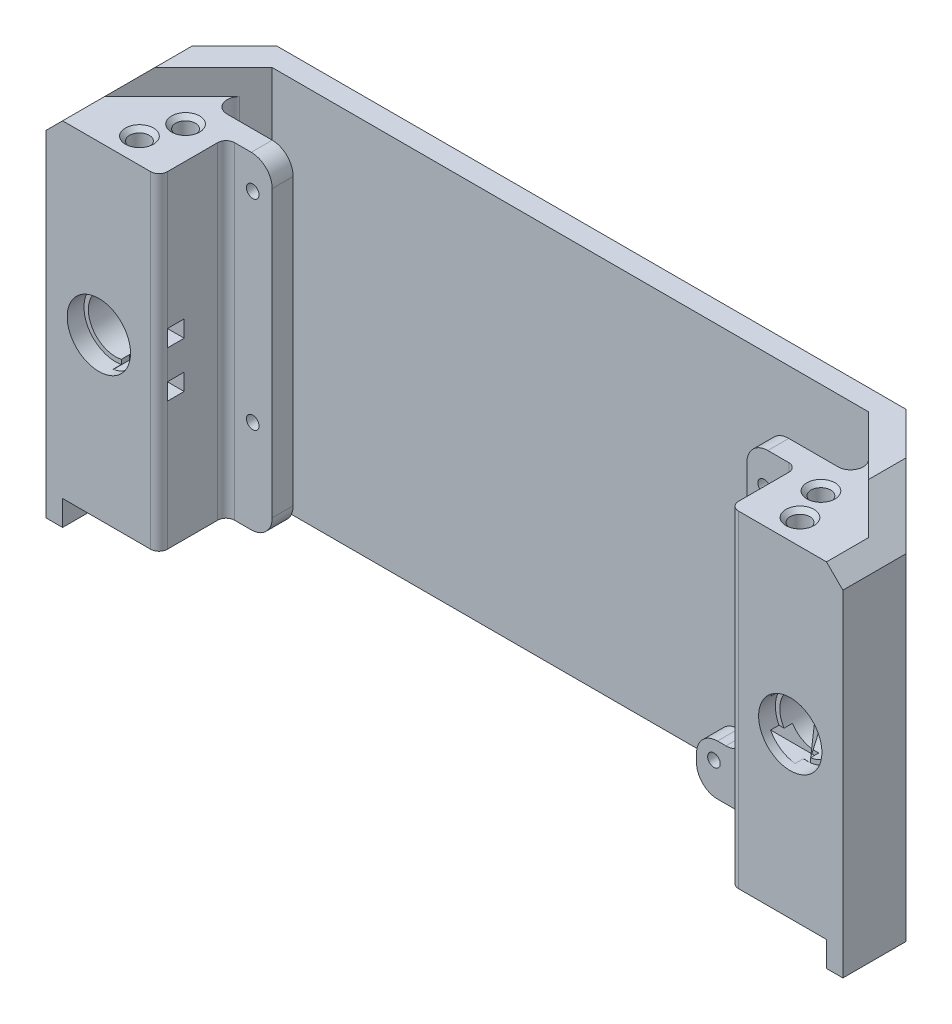
SolidWorks part; units mm, degrees
ref_plane "Front Plane" through (0, 0, 0) normal (0, 0, 1) x (1, 0, 0)
ref_plane "Top Plane" through (0, 0, 0) normal (0, 1, 0) x (1, 0, 0)
ref_plane "Right Plane" through (0, 0, 0) normal (1, 0, 0) x (0, 0, -1)
sketch "Sketch1" plane through (0, 0, 0) normal (0, 0, 1) x (1, 0, 0)
  line L1 (-95, 45) -> (95, 45)
  line L2 (-95, 45) -> (-95, -45)
  line L3 (-95, -45) -> (95, -45)
  line L4 (95, 45) -> (95, -45)
  line L5 (-95, 45) -> (95, -45) construction
  line L6 (-95, -45) -> (95, 45) construction
  point P0 (0, 0)
  point P6 (0, 0)
  dimension "D2" = 190
  dimension "D4" = 90
extrude "Boss-Extrude1" add sketch "Sketch1" along normal blind 5
sketch "Sketch2" plane through (0, 0, 5) normal (0, 0, 1) x (1, 0, 0)
  line L0 (-95, -45) -> (95, -45) construction
  line L1 (-95, 45) -> (-91.1, 45)
  line L2 (-95, 45) -> (-95, -45)
  line L3 (-95, -45) -> (-91.1, -45)
  line L4 (-91.1, 45) -> (-91.1, -45)
  line L5 (0, 0) -> (0, 45) construction
  line L6 (95, 45) -> (-95, 45) construction
  line L7 (95, -45) -> (91.1, -45)
  line L8 (91.1, 45) -> (91.1, -45)
  line L9 (95, 45) -> (91.1, 45)
  line L10 (95, 45) -> (95, -45)
  dimension "D1" = 3.9
extrude "Boss-Extrude2" add sketch "Sketch2" along normal blind 30
sketch "Sketch3" plane through (0, 45, 0) normal (0, 1, 0) x (1, 0, 0)
  line L0 (-91.1, -35) -> (-91.1, -5) construction
  line L1 (-91.1, -14) -> (-57.1, -14)
  line L2 (-91.1, -14) -> (-91.1, -19)
  line L3 (-91.1, -19) -> (-57.1, -19)
  line L4 (-57.1, -14) -> (-57.1, -19)
  line L5 (91.1, -35) -> (91.1, -5) construction
  line L6 (91.1, -14) -> (44.1, -14)
  line L7 (91.1, -14) -> (91.1, -19)
  line L8 (91.1, -19) -> (44.1, -19)
  line L9 (44.1, -14) -> (44.1, -19)
  line L10 (91.1, -5) -> (-91.1, -5) construction
  dimension "D1" = 9
  dimension "D2" = 9
  dimension "D3" = 5
  dimension "D4" = 5
  dimension "D5" = 34
  dimension "D6" = 47
extrude "Boss-Extrude3" add sketch "Sketch3" against normal up to surface (90 mm away) up to face at (0, -45, 18.75)
sketch "Sketch4" plane through (0, 0, 19) normal (0, 0, 1) x (1, 0, 0)
  line L0 (91.1, -45) -> (91.1, 45) construction
  line L1 (-91.1, 45) -> (91.1, 45)
  line L2 (-91.1, 45) -> (-91.1, 39)
  line L3 (-91.1, 39) -> (91.1, 39)
  line L4 (91.1, 45) -> (91.1, 39)
  line L5 (0, 0) -> (-91.1, 0) construction
  line L6 (-91.1, -45) -> (-91.1, 45) construction
  line L7 (-91.1, -39) -> (91.1, -39)
  line L8 (91.1, -45) -> (91.1, -39)
  line L9 (-91.1, -45) -> (91.1, -45)
  line L10 (-91.1, -45) -> (-91.1, -39)
  dimension "D1" = 6
extrude "Cut-Extrude1" cut sketch "Sketch4" against normal blind 5
sketch "Sketch5" plane through (0, 0, 19) normal (0, 0, 1) x (1, 0, 0)
  line L0 (0, 0) -> (-61.75, 0) construction
  line L1 (-70.2, 37.38) -> (70.2, 37.38) construction
  line L2 (-70.2, 37.38) -> (-70.2, -37.38) construction
  line L3 (-70.2, -37.38) -> (70.2, -37.38) construction
  line L4 (70.2, 37.38) -> (70.2, -37.38) construction
  line L5 (-70.2, 37.38) -> (70.2, -37.38) construction
  line L6 (-70.2, -37.38) -> (70.2, 37.38) construction
  line L7 (-61.75, 0) -> (-61.75, 31.13) construction
  line L8 (-61.75, 0) -> (-61.75, -16.61) construction
  line L9 (48.25, 0) -> (60.23, 0) construction
  line L10 (60.23, 0) -> (60.23, 31.13) construction
  line L11 (0, 0) -> (48.25, 0) construction
  line L12 (48.25, 0) -> (48.25, -31.38) construction
  circle A0 centre (-61.75, 31.13) radius 1.5
  circle A1 centre (-61.75, -16.61) radius 1.5
  circle A2 centre (60.23, 31.13) radius 1.5
  circle A3 centre (48.25, -31.38) radius 1.5
  point P0 (0, 0)
  dimension "D10" = 3
  dimension "D11" = 3
  dimension "D12" = 3
  dimension "D13" = 3
  dimension "D1" = 140.4
  dimension "D2" = 74.76
  dimension "D3" = 61.75
  dimension "D4" = 31.13
  dimension "D5" = 16.61
  dimension "D6" = 60.23
  dimension "D7" = 31.13
  dimension "D8" = 48.25
  dimension "D9" = 31.38
extrude "Cut-Extrude2" cut sketch "Sketch5" against normal up to surface (5 mm away) up to face at (67.6, 0, 14)
sketch "Sketch6" plane through (0, 0, 19) normal (0, 0, 1) x (1, 0, 0)
  line L1 (44.1, 39) -> (56.1, 39)
  line L2 (44.1, 39) -> (44.1, -27)
  line L3 (44.1, -27) -> (56.1, -27)
  line L4 (56.1, 39) -> (56.1, -27)
  dimension "D1" = 12
  dimension "D2" = 66
extrude "Cut-Extrude3" cut sketch "Sketch6" against normal up to surface (5 mm away) up to face at (46.75, -31.38, 14)
chamfer "Chamfer6" distance 20 angle 45 4 edges at (91.1, 0, 5) (95, 0, 0) (-95, 0, 0) (-91.1, 0, 5)
sketch "Sketch7" plane through (0, 39, 0) normal (0, 1, 0) x (1, 0, 0)
  line L0 (-85.1, -19) -> (-91.1, -25)
  line L1 (-91.1, -25) -> (-91.1, -35)
  line L2 (-91.1, -35) -> (-68.1, -35)
  line L3 (-68.1, -35) -> (-68.1, -19)
  line L4 (-85.1, -19) -> (-57.1, -19) construction
  line L5 (-68.1, -19) -> (-85.1, -19)
  line L6 (0, 0) -> (0, -5) construction
  line L7 (71.1, -5) -> (-71.1, -5) construction
  line L8 (68.1, -35) -> (68.1, -19)
  line L9 (91.1, -35) -> (68.1, -35)
  line L10 (91.1, -25) -> (91.1, -35)
  line L11 (85.1, -19) -> (91.1, -25)
  line L12 (68.1, -19) -> (85.1, -19)
  dimension "D1" = 23
extrude "Boss-Extrude4" add sketch "Sketch7" against normal up to surface (78 mm away) up to face at (-69.85, -39, 16.5)
fillet "Fillet4" radius 5 6 edges at (-57.1, -39, 16.5) (-57.1, 39, 16.5) (56.1, 39, 16.5) (44.1, -39, 16.5) (44.1, -27, 16.5) (56.1, -27, 16.5)
fillet "Fillet5" radius 2 4 edges at (-68.1, 0, 35) (68.1, 0, 35) (68.1, 0, 19) (-68.1, 0, 19)
fillet "Fillet6" radius 3 2 edges at (-80.1, 0, 14) (80.1, 0, 14)
sketch "Sketch9" plane through (0, 0, 35) normal (0, 0, 1) x (1, 0, 0)
  line L6 (0, 0) -> (0, -45) construction
  line L7 (-71.1, -45) -> (71.1, -45) construction
  line L8 (-95, 45) -> (-95, -45) construction
  line L9 (-95, 39) -> (-82.45, 39) construction
  line L10 (-95, 39) -> (-95, -0.9074) construction
  line L11 (-95, -0.9074) -> (-82.45, -0.9074) construction
  line L12 (-82.45, 39) -> (-82.45, -0.9074) construction
  line L13 (-91.1, 39) -> (-70.1, 39) construction
  circle A0 centre (-82.45, -0.9074) radius 6.5
  circle A1 centre (82.45, -0.9074) radius 6.5
  dimension "D3" = 13
  dimension "D1" = 39.9074
  dimension "D2" = 12.55
extrude "Cut-Extrude4" cut sketch "Sketch9" against normal blind 10
sketch "Sketch10" plane through (0, 0, 35) normal (0, 0, 1) x (1, 0, 0)
  circle A0 centre (-82.45, -0.9074) radius 7.55
  circle A1 centre (82.45, -0.9074) radius 7.55
  dimension "D1" = 15.1
  dimension "D2" = 15.1
extrude "Cut-Extrude5" cut sketch "Sketch10" against normal blind 4
sketch "Sketch12" plane through (-68.1, 0, 0) normal (1, 0, 0) x (0, 0, -1)
  line L0 (-33, -4.4074) -> (-29, -4.4074)
  line L1 (-33, 39) -> (-23, 39) construction
  line L2 (-33, 39) -> (-33, -0.9074) construction
  line L3 (-33, -0.9074) -> (-23, -0.9074) construction
  line L4 (-23, 39) -> (-23, -0.9074) construction
  line L5 (-33, 6.5926) -> (-23, 6.5926) construction
  line L6 (-33, 6.5926) -> (-33, -8.4074) construction
  line L7 (-33, -8.4074) -> (-23, -8.4074) construction
  line L8 (-23, 6.5926) -> (-23, -8.4074) construction
  line L9 (-33, 6.5926) -> (-23, -8.4074) construction
  line L10 (-33, -8.4074) -> (-23, 6.5926) construction
  line L11 (-33, 6.5926) -> (-29, 6.5926)
  line L12 (-33, 6.5926) -> (-33, 2.5926)
  line L13 (-33, 2.5926) -> (-29, 2.5926)
  line L14 (-29, 6.5926) -> (-29, 2.5926)
  line L15 (-29, -8.4074) -> (-29, -4.4074)
  line L16 (-33, -8.4074) -> (-29, -8.4074)
  line L17 (-33, -8.4074) -> (-33, -4.4074)
  point P5 (-28, -0.9074)
  dimension "D1" = 39.9074
  dimension "D2" = 10
  dimension "D3" = 15
  dimension "D4" = 10
  dimension "D5" = 4
  dimension "D6" = 4
extrude "Cut-Extrude6" cut sketch "Sketch12" against normal blind 13 and the other way blind 151.4
sketch "Sketch15" plane through (0, 39, 0) normal (0, 1, 0) x (1, 0, 0)
  line L0 (68.1, -21) -> (68.1, -33) construction
  line L5 (72.8574, -14) -> (61.1, -14) construction
  line L6 (91.1, -35) -> (68.1, -35) construction
  line L7 (91.1, -35) -> (91.1, -14) construction
  line L8 (91.1, -14) -> (68.1, -14) construction
  line L9 (68.1, -35) -> (68.1, -14) construction
  line L10 (68.1, -14) -> (75.7667, -21) construction
  line L11 (75.7667, -21) -> (83.4333, -28) construction
  line L12 (83.4333, -28) -> (91.1, -35) construction
  line L13 (0, 0) -> (0, -5) construction
  line L14 (71.1, -5) -> (-71.1, -5) construction
  line L15 (75.7667, -21) -> (75.7667, -29) construction
  line L16 (75.7667, -29) -> (78.7667, -29) construction
  circle A0 centre (75.7667, -21) radius 2.35
  circle A1 centre (83.4333, -28) radius 2.35 construction
  circle A2 centre (-75.7667, -21) radius 2.35
  circle A3 centre (-83.4333, -28) radius 2.35 construction
  circle A6 centre (78.7667, -29) radius 2.35
  circle A7 centre (-78.7667, -29) radius 2.35
  dimension "D1" = 4.7
  dimension "D2" = 4.7
  dimension "D5" = 4.7
  dimension "D3" = 23
  dimension "D4" = 21
  dimension "D6" = 8
  dimension "D7" = 3
extrude "Cut-Extrude7" cut sketch "Sketch15" against normal blind 8
chamfer "Chamfer7" distance 1 angle 45 4 edges at (-75.7667, 39, 18.65) (75.7667, 39, 23.35) (-78.7667, 39, 26.65) (78.7667, 39, 31.35)
sketch "Sketch17" plane through (0, -39, 0) normal (0, -1, 0) x (1, 0, 0)
  line L0 (0, 0) -> (0, 5) construction
  line L1 (91.1, 35) -> (68.1, 35) construction
  line L2 (91.1, 35) -> (91.1, 19) construction
  line L3 (91.1, 19) -> (68.1, 19) construction
  line L4 (68.1, 35) -> (68.1, 19) construction
  line L5 (-71.1, 5) -> (71.1, 5) construction
  line L6 (68.1, 33) -> (68.1, 21) construction
  line L7 (66.1, 19) -> (49.1, 19) construction
  circle A0 centre (79.6, 27) radius 6.1
  circle A1 centre (-79.6, 27) radius 6.1
  dimension "D2" = 12.2
  dimension "D1" = 11.5
  dimension "D3" = 8
  dimension "D4" = 11.5
extrude "Cut-Extrude8" cut sketch "Sketch17" against normal blind 3.2
fillet "Fillet7" radius 0.2 2 edges at (-85.7, -39, 27) (85.7, -39, 27)
chamfer "Chamfer8" distance 9.9 angle 45 2 edges at (-95, 45, 27.5) (95, 45, 27.5)
